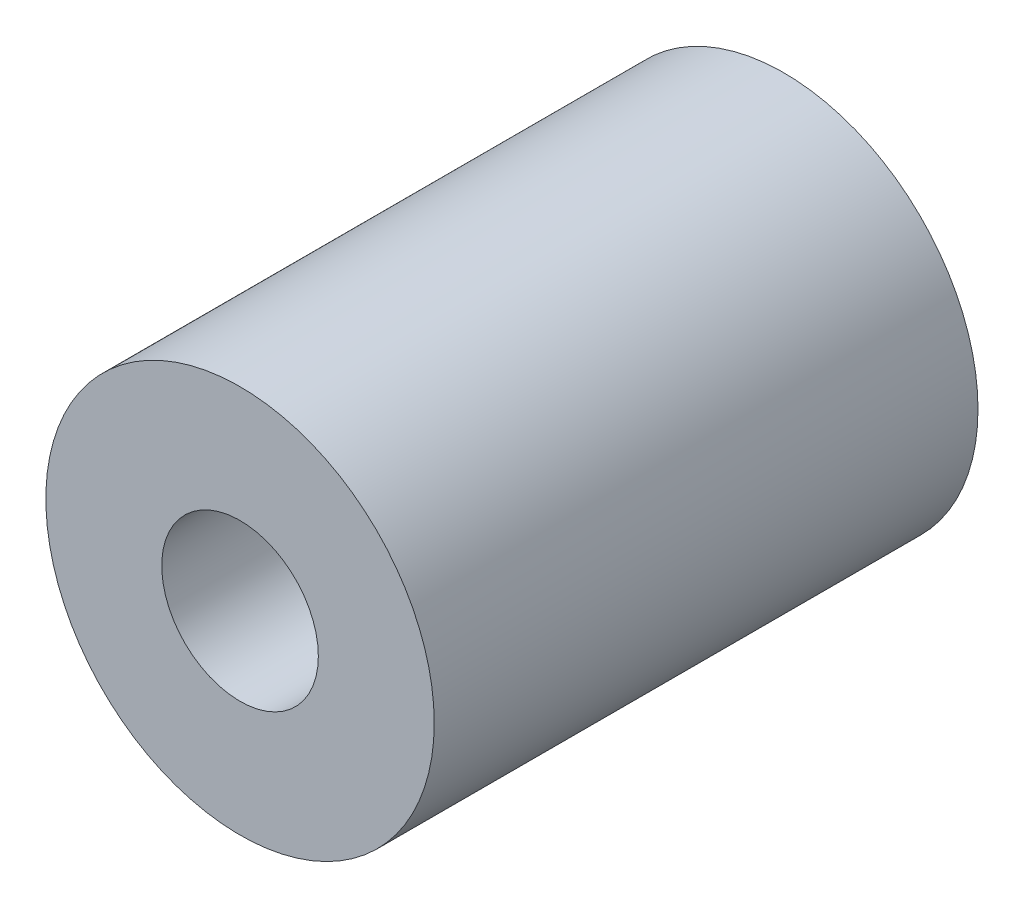
SolidWorks part; units mm, degrees
ref_plane "Front Plane" through (0, 0, 0) normal (0, 0, 1) x (1, 0, 0)
ref_plane "Top Plane" through (0, 0, 0) normal (0, 1, 0) x (1, 0, 0)
ref_plane "Right Plane" through (0, 0, 0) normal (1, 0, 0) x (0, 0, -1)
sketch "Sketch1" plane through (0, 0, 0) normal (0, 0, 1) x (1, 0, 0)
  circle A0 centre (0, 0) radius 7.9375
  circle A1 centre (0, 0) radius 3.2004
  dimension "OD" = 15.875
  dimension "ID" = 6.4008
extrude "Extrude1" add sketch "Sketch1" along normal mid plane 22.225
sketch "Sketch2" plane through (0, 0, 0) normal (1, 0, 0) x (0, 0, -1)
  line L0 (-11.1125, -3.2004) -> (11.1125, -3.2004) construction
  line L3 (11.1125, 3.2004) -> (-11.1125, 3.2004) construction
  line L5 (-11.1125, -3.2004) -> (11.1125, -3.2004)
  line L6 (11.1125, 3.2004) -> (-11.1125, 3.2004)
sketch "Sketch4" plane through (0, 0, 11.1125) normal (0, 0, 1) x (1, 0, 0)
  line L0 (0, 0) -> (-2.263, 2.263)
  line L1 (0, -1.7463) -> (0, 1.7463) construction
  circle A0 centre (0, 0) radius 3.2004 construction
  dimension "D1" = 45
